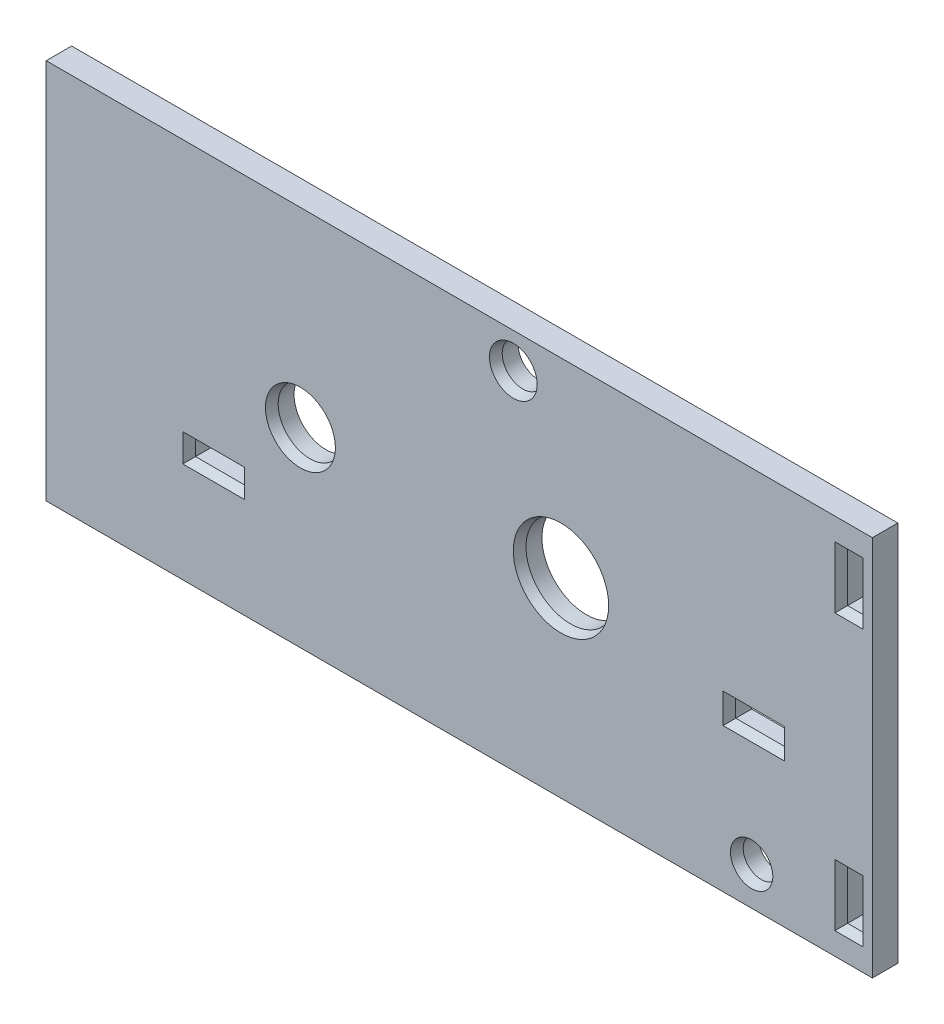
SolidWorks part; units mm, degrees
ref_plane "Front Plane" through (0, 0, 0) normal (0, 0, 1) x (1, 0, 0)
ref_plane "Top Plane" through (0, 0, 0) normal (0, 1, 0) x (1, 0, 0)
ref_plane "Right Plane" through (0, 0, 0) normal (1, 0, 0) x (0, 0, -1)
sketch "Sketch1" plane through (0, 0, 0) normal (0, 0, 1) x (1, 0, 0)
  line L0 (-55.3, -10.3) -> (-55.3, -13.7)
  line L1 (-86, -30) -> (44, -30)
  line L2 (-86, -30) -> (-86, 30)
  line L3 (-86, 30) -> (44, 30)
  line L4 (44, -30) -> (44, 30)
  line L5 (-64, -10.3) -> (-55.3, -10.3)
  line L6 (-64, -10.3) -> (-64, -13.7)
  line L7 (-64, -13.7) -> (-55.3, -13.7)
  line L13 (29.7, -5) -> (21, -5) construction
  line L14 (-55.3, -12) -> (-64, -12) construction
  line L15 (-59.65, -10.3) -> (-59.65, -13.7) construction
  line L16 (40.3, 26) -> (40.3, 17.3) construction
  line L17 (38.6, 26) -> (42, 26)
  line L18 (38.6, 26) -> (38.6, 17.3)
  line L19 (38.6, 17.3) -> (42, 17.3)
  line L20 (42, 26) -> (42, 17.3)
  line L21 (38.6, -17.3) -> (42, -17.3)
  line L22 (38.6, -17.3) -> (38.6, -26)
  line L23 (38.6, -26) -> (42, -26)
  line L24 (42, -17.3) -> (42, -26)
  line L25 (42, 21.65) -> (38.6, 21.65) construction
  line L26 (40.3, -17.3) -> (40.3, -26) construction
  line L27 (42, -21.65) -> (38.6, -21.65) construction
  line L28 (21, -3.15) -> (29.7, -3.15)
  line L29 (21, -3.15) -> (21, -6.85)
  line L30 (21, -6.85) -> (29.7, -6.85)
  line L31 (29.7, -3.15) -> (29.7, -6.85)
  line L32 (25.35, -6.85) -> (25.35, -3.15) construction
  circle A2 centre (-46, 0) radius 5
  circle A3 centre (-12.5, 24.5) radius 3.25
  circle A4 centre (25, -24) radius 2.83
  circle A5 centre (-5, 0) radius 7
  point P1 (0, 0)
  point P24 (-86, 0)
  dimension "D10" = 6.5
  dimension "D14" = 5.66
  dimension "D21" = 10
  dimension "D22" = 14
  dimension "D2" = 60
  dimension "D4" = 130
  dimension "D6" = 8.7
  dimension "D8" = 3.4
  dimension "D12" = 111
  dimension "D19" = 24.5
  dimension "D13" = 24
  dimension "D5" = 40
  dimension "D7" = 33.5
  dimension "D9" = 7.5
  dimension "D11" = 26.35
  dimension "D15" = 126.3
  dimension "D17" = 21.65
  dimension "D18" = 21.65
  dimension "D16" = 85
  dimension "D3" = 5
  dimension "D20" = 12
extrude "Boss-Extrude1" add sketch "Sketch1" along normal mid plane 4
sketch "Sketch2" plane through (0, 0, 2) normal (0, 0, 1) x (1, 0, 0)
  line L0 (40.3, 26) -> (40.3, 17.3) construction
  line L1 (42, 21.65) -> (38.6, 21.65) construction
  line L2 (40.3, -17.3) -> (40.3, -26) construction
  line L3 (42, -17.3) -> (38.6, -17.3) construction
  line L4 (38.6, -26) -> (42, -26) construction
  line L5 (38.6, -21.65) -> (42, -21.65) construction
  line L6 (38.6, -17.3) -> (38.6, -26) construction
  line L7 (42, -26) -> (42, -17.3) construction
sketch "Sketch4" plane through (0, 0, -2) normal (0, 0, -1) x (-1, 0, 0)
  line L0 (59.65, -10.3) -> (59.65, -13.7) construction
  line L1 (55.3, -12) -> (64, -12) construction
  line L2 (-29.7, -5) -> (-21, -5) construction
  line L3 (-29.7, -6.85) -> (-29.7, -3.15) construction
  line L4 (-21, -3.15) -> (-21, -6.85) construction
  line L5 (-25.35, -3.15) -> (-25.35, -6.85) construction
  line L6 (-29.7, -3.15) -> (-21, -3.15) construction
  line L7 (-21, -6.85) -> (-29.7, -6.85) construction
chamfer "Chamfer1" distance 0.5 distance2 1.5 20 edges at (40.3, -26, 2) (42, -21.65, 2) (40.3, -17.3, 2) (38.6, -21.65, 2) (2, 0, 2) (27.83, -24, 2) (-41, 0, 2) (-9.25, 24.5, 2) (-59.65, -13.7, 2) (-55.3, -12, 2) (-59.65, -10.3, 2) (-64, -12, 2) (25.35, -6.85, 2) (29.7, -5, 2) (25.35, -3.15, 2) (21, -5, 2) (40.3, 17.3, 2) (42, 21.65, 2) (40.3, 26, 2) (38.6, 21.65, 2) first distance on face at (40.3, 21.65, 2)
equation "\"padding\"=4"
equation "\"hole_width\"=3.4"
equation "\"hole_height\"=8.7"
equation "\"back_boost\"= 7"
equation "\"D5@Sketch1\"=33+\"back_boost\""
equation "\"D12@Sketch1\"=104+\"back_boost\""
equation "\"D15@Sketch1\"=119.30mm+\"back_boost\""
equation "\"D11@Sketch1\"=\"back_boost\"+19.35mm"
equation "\"D4@Sketch1\"=\"back_boost\"+123.00mm"
equation "\"pin_hole_height\"=9.2"
equation "\"pin_hole_width\"=3.53"
